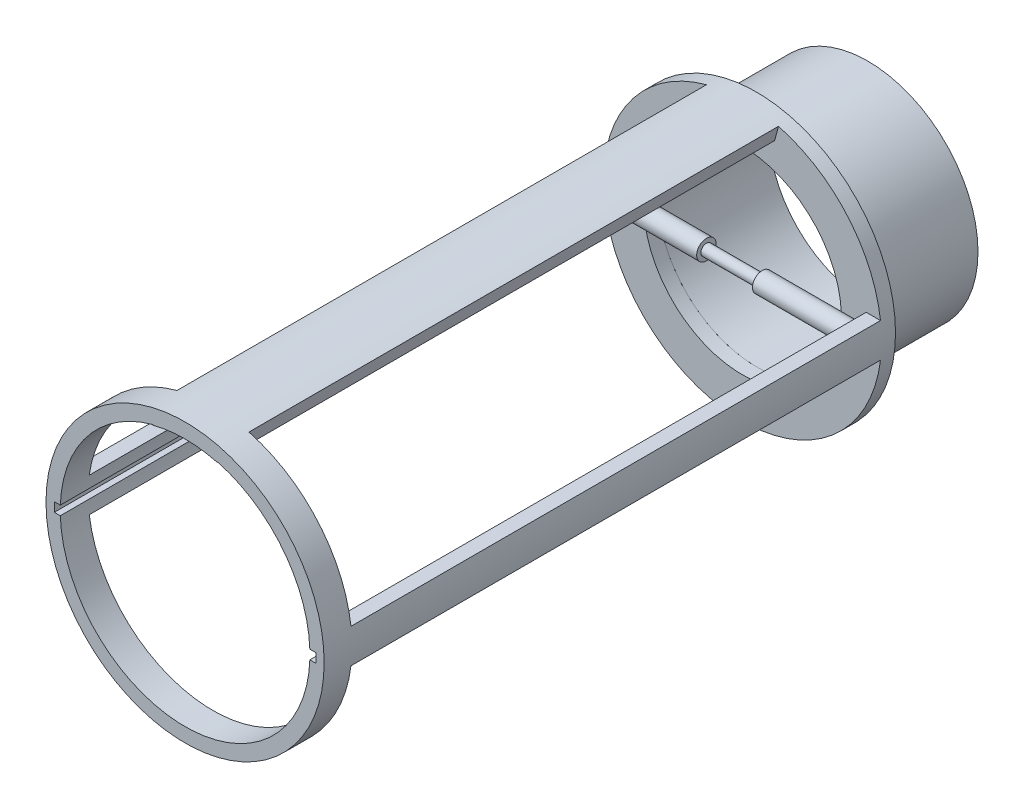
SolidWorks part; units mm, degrees
ref_plane "Front Plane" through (0, 0, 0) normal (0, 0, 1) x (1, 0, 0)
ref_plane "Top Plane" through (0, 0, 0) normal (0, 1, 0) x (1, 0, 0)
ref_plane "Right Plane" through (0, 0, 0) normal (1, 0, 0) x (0, 0, -1)
sketch "Sketch1" plane through (0, 0, 0) normal (0, 0, 1) x (1, 0, 0)
  circle A0 centre (0, 0) radius 19.75
  circle A1 centre (0, 0) radius 17.75
  dimension "D1" = 39.5
  dimension "D2" = 35.5
extrude "Boss-Extrude1" add sketch "Sketch1" along normal blind 20
sketch "Sketch2" plane through (0, 0, 20) normal (0, 0, 1) x (1, 0, 0)
  circle A0 centre (0, 0) radius 24.95
  circle A2 centre (0, 0) radius 17.75 construction
  circle A3 centre (0, 0) radius 17.75
  dimension "D1" = 49.9
extrude "Boss-Extrude2" add sketch "Sketch2" along normal blind 2.5 separate body
sketch "Sketch3" plane through (0, 0, 22.5) normal (0, 0, 1) x (1, 0, 0)
  circle A0 centre (0, 0) radius 24.95 construction
  circle A1 centre (0, 0) radius 24.95
  circle A2 centre (0, 0) radius 22.4
  dimension "D1" = 44.8
extrude "Boss-Extrude3" add sketch "Sketch3" along normal blind 100
sketch "Sketch4" plane through (0, 0, 122.5) normal (0, 0, 1) x (1, 0, 0)
  line L1 (-23.45, 0.825) -> (23.45, 0.825)
  line L2 (-23.45, 0.825) -> (-23.45, -0.825)
  line L3 (-23.45, -0.825) -> (23.45, -0.825)
  line L4 (23.45, 0.825) -> (23.45, -0.825)
  circle A0 centre (0, 0) radius 24.95 construction
  point P6 (0, 0.825)
  point P7 (23.45, 0)
  dimension "D1" = 1.65
  dimension "D2" = 46.9
extrude "Cut-Extrude1" cut sketch "Sketch4" against normal blind 100
sketch "Sketch6" plane through (0, 0, 122.5) normal (0, 0, 1) x (1, 0, 0)
  line L0 (-24.7604, 3.0698) -> (-22.1887, 3.0698)
  line L2 (24.7598, -3.0746) -> (22.188, -3.0746)
  line L3 (22.1887, 3.0698) -> (24.7604, 3.0698)
  line L4 (-22.188, -3.0746) -> (-24.7598, -3.0746)
  arc A0 (22.3848, 0.825) -> (-22.3848, 0.825) centre (0, 0) ccw construction
  arc A1 (22.1887, 3.0698) -> (-22.1887, 3.0698) centre (0, 0) ccw
  arc A2 (-22.3848, -0.825) -> (22.3848, -0.825) centre (0, 0) ccw construction
  arc A3 (-22.188, -3.0746) -> (22.188, -3.0746) centre (0, 0) ccw
  circle A4 centre (0, 0) radius 24.95 construction
  arc A5 (-24.7598, -3.0746) -> (24.7598, -3.0746) centre (0, 0) ccw
  arc A6 (24.7604, 3.0698) -> (-24.7604, 3.0698) centre (0, 0) ccw
extrude "Cut-Extrude3" cut sketch "Sketch6" against normal blind 95 from offset 5 offset against normal yes
sketch "Sketch7" plane through (-23.45, 0, 0) normal (1, 0, 0) x (0, 0, -1)
  circle A0 centre (-24.0194, 0) radius 1.75
extrude "Boss-Extrude4" add sketch "Sketch7" along normal blind 18.5
sketch "Sketch9" plane through (-4.95, 0, 0) normal (1, 0, 0) x (0, 0, -1)
  circle A0 centre (-24.0194, 0) radius 1
extrude "Boss-Extrude5" add sketch "Sketch9" along normal blind 10
sketch "Sketch10" plane through (5.05, 0, 0) normal (1, 0, 0) x (0, 0, -1)
  circle A0 centre (-24.0194, 0) radius 1.75 construction
  circle A1 centre (-24.0194, 0) radius 1.75
extrude "Boss-Extrude6" add sketch "Sketch10" along normal up to surface (18.4 mm away) up to face at (23.45, 0, 72.5)
sketch "Sketch13" plane through (0, 0, 122.5) normal (0, 0, 1) x (1, 0, 0)
  line L5 (5.7717, 21.5401) -> (6.4575, 24.0998)
  line L7 (-5.7717, 21.5401) -> (-6.4575, 24.0998)
  circle A1 centre (0, 0) radius 24.95 construction
  arc A6 (5.7717, 21.5401) -> (-5.7717, 21.5401) centre (0, 0) ccw
  arc A8 (6.4575, 24.0998) -> (-6.4575, 24.0998) centre (0, 0) ccw
extrude "Boss-Extrude7" add sketch "Sketch13" against normal up to surface (100 mm away) up to face at (0, 6.8149, 22.5)
